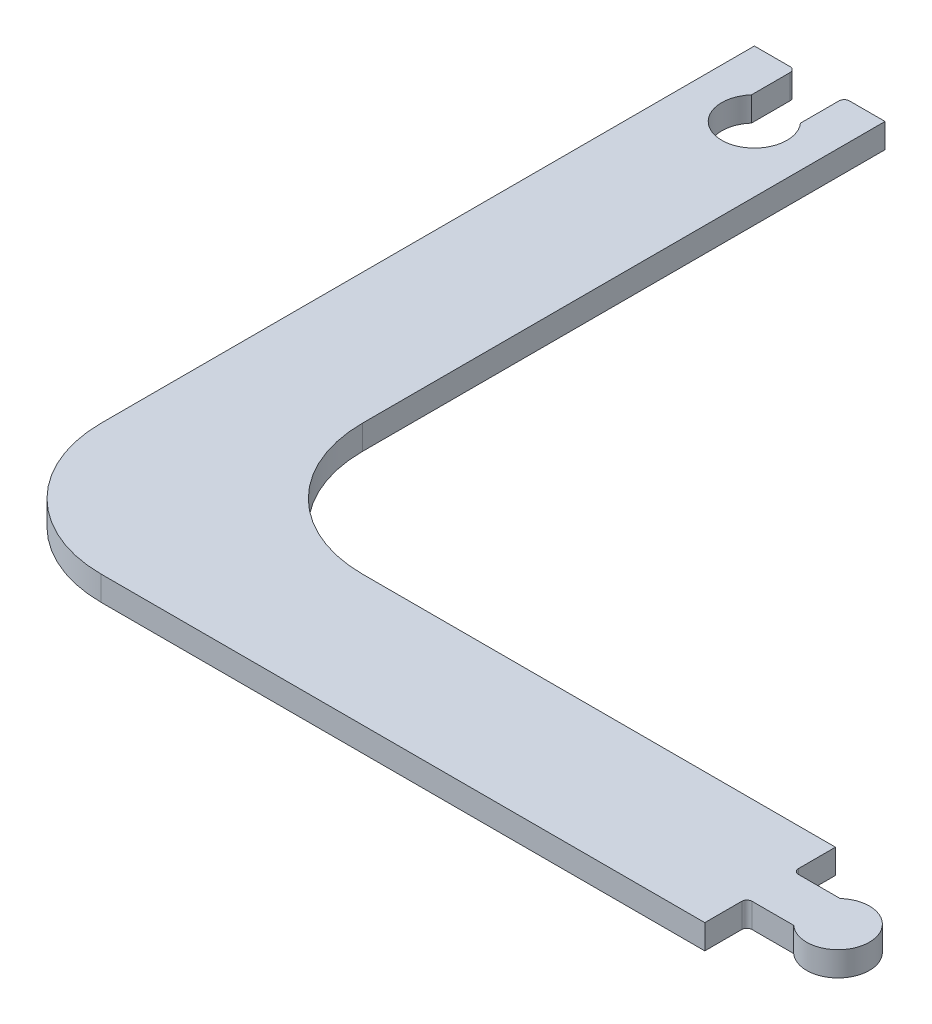
SolidWorks part; units mm, degrees
ref_plane "Front Plane" through (0, 0, 0) normal (0, 0, 1) x (1, 0, 0)
ref_plane "Top Plane" through (0, 0, 0) normal (0, 1, 0) x (1, 0, 0)
ref_plane "Right Plane" through (0, 0, 0) normal (1, 0, 0) x (0, 0, -1)
sketch "Sketch1" plane through (0, 0, 0) normal (0, 1, 0) x (1, 0, 0)
  line L0 (12.7, 146.05) -> (12.7, 12.7) construction
  line L1 (25.4, 0) -> (142.7605, 0)
  line L2 (0, 25.4) -> (0, 152.4)
  line L3 (0, 152.4) -> (6.9375, 152.4)
  line L7 (142.7605, 25.4) -> (50.8, 25.4)
  line L8 (25.4, 152.4) -> (25.4, 50.8)
  line L9 (152.4, 12.7) -> (146.05, 12.7) construction
  line L10 (17.4625, 151.4) -> (17.4625, 143.9001)
  line L11 (7.9375, 151.4) -> (7.9375, 143.9001)
  line L12 (18.4625, 152.4) -> (25.4, 152.4)
  line L16 (146.05, 12.7) -> (12.7, 12.7) construction
  line L17 (143.7605, 8.1875) -> (151.856, 8.1875)
  line L18 (143.7605, 17.2125) -> (151.856, 17.2125)
  line L19 (142.7605, 25.4) -> (142.7605, 18.2125)
  line L20 (142.7605, 7.1875) -> (142.7605, 0)
  arc A0 (0, 25.4) -> (25.4, 0) centre (25.4, 25.4) ccw
  arc A1 (25.4, 50.8) -> (50.8, 25.4) centre (50.8, 50.8) ccw
  arc A2 (7.9375, 143.9001) -> (17.4625, 143.9001) centre (12.7, 139.7) ccw
  arc A4 (151.856, 8.1875) -> (151.856, 17.2125) centre (155.9605, 12.7) ccw
  arc A5 (142.7605, 7.1875) -> (143.7605, 8.1875) centre (143.7605, 7.1875) cw
  arc A6 (142.7605, 18.2125) -> (143.7605, 17.2125) centre (143.7605, 18.2125) ccw
  arc A7 (18.4625, 152.4) -> (17.4625, 151.4) centre (18.4625, 151.4) ccw
  arc A8 (6.9375, 152.4) -> (7.9375, 151.4) centre (6.9375, 151.4) cw
  point P9 (0, 0)
  point P28 (0, 0)
  point P33 (17.4625, 152.4)
  dimension "D3" = 25.4
  dimension "D6" = 12.7
  dimension "D7" = 12.7
  dimension "D4" = 13.2
  dimension "D12" = 1
  dimension "D13" = 6.1
  dimension "D1" = 25.4
  dimension "D2" = 25.4
  dimension "D5" = 152.4
  dimension "D8" = 9.525
  dimension "D9" = 4.7625
  dimension "D10" = 9.025
  dimension "D11" = 4.5125
extrude "Boss-Extrude1" add sketch "Sketch1" along normal blind 4.7625
